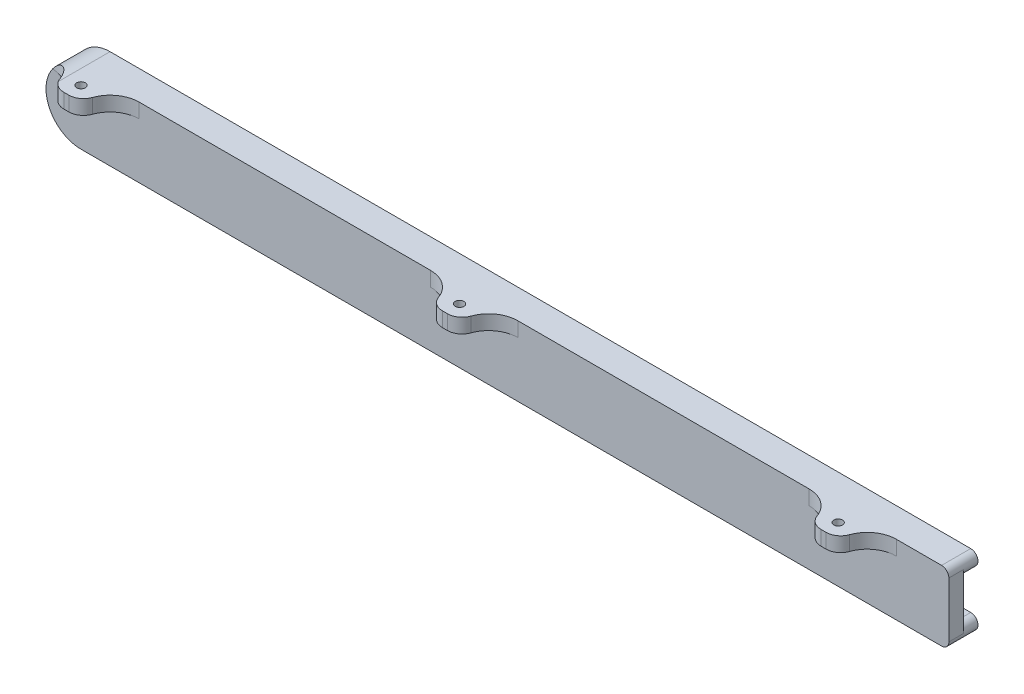
SolidWorks part; units mm, degrees
ref_plane "Plan de face" through (0, 0, 0) normal (0, 0, 1) x (1, 0, 0)
ref_plane "Plan de dessus" through (0, 0, 0) normal (0, 1, 0) x (1, 0, 0)
ref_plane "Plan de droite" through (0, 0, 0) normal (1, 0, 0) x (0, 0, -1)
sketch "Esquisse1" plane through (0, 0, 0) normal (0, 0, 1) x (1, 0, 0)
  line L0 (-155, 12) -> (-155, -12)
  line L1 (-155, 7) -> (155, 7)
  line L2 (-150, 7) -> (-150, -7)
  line L3 (-150, -7) -> (150, -7)
  line L4 (150, 7) -> (150, -7) construction
  line L5 (-150, 7) -> (150, -7) construction
  line L6 (-150, -7) -> (150, 7) construction
  line L7 (-155, -12) -> (155, -12)
  line L8 (155, 12) -> (155, -12) construction
  line L9 (-155, 12) -> (155, 12)
  line L10 (150, 7) -> (155, 7)
  line L11 (150, -7) -> (155, -7)
  line L12 (-150, 7) -> (150, 7) construction
  line L13 (155, 12) -> (155, 7)
  line L14 (155, -7) -> (155, -12)
  point P0 (0, 0)
  dimension "14" = 14
  dimension "D2" = 300
  dimension "D3" = 5
extrude "Boss.-Extru.1" add sketch "Esquisse1" along normal blind 10 contours L14 L11 L3 L2 L1 L0 L7 | L13 L9 L0 L1 region at (0, 9.5, 0) region at (-6.5895, -9.0895, 0)
sketch "Esquisse2" plane through (155, 0, 0) normal (1, 0, 0) x (0, 0, -1)
  line L0 (-10, -12) -> (-10, 12)
  line L1 (-10, 12) -> (-5, 12)
  line L2 (-10, 12) -> (0, 12) construction
  line L3 (-5, 12) -> (-5, -12)
  line L4 (-10, -12) -> (0, -12) construction
  line L5 (-10, -12) -> (-5, -12)
  dimension "D1" = 5
extrude "Boss.-Extru.2" add sketch "Esquisse2" against normal through all
fillet "Congé1" 2 edges at (-155, 12, 5) (-155, -12, 5) type full round first side face at (0, 12, 5) second side face at (0, -12, 5) middle face at (-155, 0, 5)
sketch "Esquisse3" plane through (0, -12, 0) normal (0, -1, 0) x (1, 0, 0)
  line L0 (-3, 20) -> (-3, 10)
  line L1 (-133, 20) -> (-143, 20)
  line L2 (-133, 20) -> (-133, 10)
  line L3 (-133, 10) -> (-143, 10)
  line L4 (-143, 20) -> (-143, 10)
  line L5 (-133, 20) -> (-143, 10) construction
  line L6 (-133, 10) -> (-143, 20) construction
  line L7 (-3, 20) -> (-13, 20)
  line L8 (-13, 20) -> (-13, 10)
  line L9 (-3, 10) -> (-13, 10)
  line L10 (127, 20) -> (127, 10)
  line L11 (127, 20) -> (117, 20)
  line L12 (117, 20) -> (117, 10)
  line L13 (127, 10) -> (117, 10)
  circle A0 centre (-138, 15) radius 1.5
  circle A1 centre (-8, 15) radius 1.5
  circle A2 centre (122, 15) radius 1.5
  point P0 (-138, 15)
  dimension "D3" = 3
  dimension "D1" = 10
  dimension "D2" = 10
  dimension "D4" = 3
extrude "Boss.-Extru.3" add sketch "Esquisse3" against normal blind 5 from offset 19 offset against normal yes
fillet "Congé2" radius 10 1 edges at (-143, 9.5, 10)
fillet "Congé3" radius 10 5 edges at (127, 9.5, 10) (117, 9.5, 10) (-3, 9.5, 10) (-13, 9.5, 10) (-133, 9.5, 10)
fillet "Congé4" 2 edges at (155, -7, 2.5) (155, -12, 5) type full round first side face at (2.5, -7, 2.5) second side face at (6, -12, 5) middle face at (155, 0, 3.75)
fillet "Congé5" 2 edges at (155, 12, 5) (155, 7, 2.5) type full round first side face at (15.8521, 12, 12.1175) second side face at (2.5, 7, 2.5) middle face at (155, 3.1667, 5)
fillet "Congé6" radius 5 6 edges at (117, 9.5, 20) (127, 9.5, 20) (-143, 9.5, 20) (-133, 9.5, 20) (-13, 9.5, 20) (-3, 9.5, 20)
